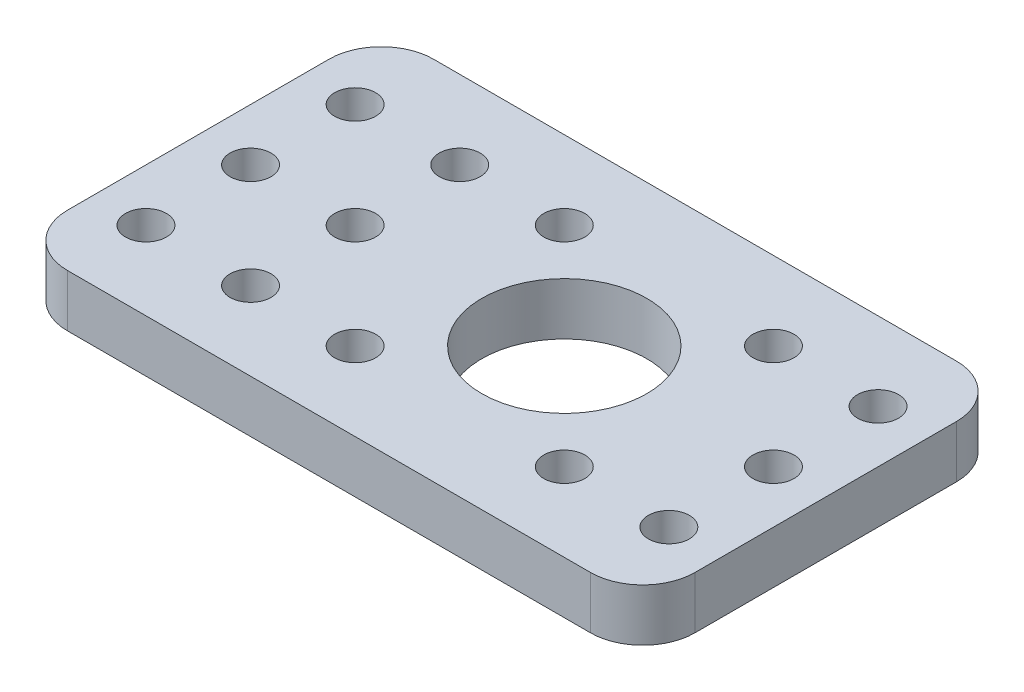
SolidWorks part; units mm, degrees
material "6061-T6 (SS)"
ref_plane "Front Plane" through (0, 0, 0) normal (0, 0, 1) x (1, 0, 0)
ref_plane "Top Plane" through (0, 0, 0) normal (0, 1, 0) x (1, 0, 0)
ref_plane "Right Plane" through (0, 0, 0) normal (1, 0, 0) x (0, 0, -1)
sketch "Sketch1" plane through (0, 0, 0) normal (0, 1, 0) x (1, 0, 0)
  line L1 (0, 0) -> (76.2, 0)
  line L2 (0, 0) -> (0, 44.45)
  line L3 (0, 44.45) -> (76.2, 44.45)
  line L4 (76.2, 0) -> (76.2, 44.45)
  dimension "D1" = 76.2
  dimension "D2" = 44.45
extrude "Boss-Extrude1" add sketch "Sketch1" along normal blind 6.35
fillet "Fillet1" radius 6.35 4 edges at (0, 3.175, -44.45) (76.2, 3.175, -44.45) (0, 3.175, 0) (76.2, 3.175, 0)
sketch "Sketch2" plane through (0, 6.35, 0) normal (0, 1, 0) x (1, 0, 0)
  line L1 (6.35, 0) -> (69.85, 0) construction
  line L3 (76.2, 6.35) -> (76.2, 38.1) construction
  circle A0 centre (31.75, 34.925) radius 2.4892 construction
  circle A1 centre (6.35, 34.925) radius 2.4892 construction
  circle A2 centre (19.05, 34.925) radius 2.4892 construction
  circle A3 centre (19.05, 22.225) radius 2.4892 construction
  circle A4 centre (6.35, 22.225) radius 2.4892 construction
  circle A5 centre (6.35, 9.525) radius 2.4892 construction
  circle A6 centre (19.05, 9.525) radius 2.4892 construction
  circle A7 centre (31.75, 9.525) radius 2.4892 construction
  circle A8 centre (57.15, 9.525) radius 2.4892 construction
  circle A9 centre (69.85, 9.525) radius 2.4892 construction
  circle A10 centre (69.85, 22.225) radius 2.4892 construction
  circle A11 centre (69.85, 34.925) radius 2.4892 construction
  circle A12 centre (57.15, 34.925) radius 2.4892 construction
  circle A14 centre (31.75, 34.925) radius 2.4892
  circle A15 centre (6.35, 34.925) radius 2.4892
  circle A16 centre (19.05, 34.925) radius 2.4892
  circle A17 centre (19.05, 22.225) radius 2.4892
  circle A18 centre (6.35, 22.225) radius 2.4892
  circle A19 centre (6.35, 9.525) radius 2.4892
  circle A20 centre (19.05, 9.525) radius 2.4892
  circle A21 centre (31.75, 9.525) radius 2.4892
  circle A22 centre (57.15, 9.525) radius 2.4892
  circle A23 centre (69.85, 9.525) radius 2.4892
  circle A24 centre (69.85, 22.225) radius 2.4892
  circle A25 centre (69.85, 34.925) radius 2.4892
  circle A26 centre (57.15, 34.925) radius 2.4892
  circle A27 centre (44.45, 22.225) radius 10.0254
  point P45 (76.2, 17.9283)
  dimension "D3" = 20.0508
  dimension "D1" = 22.225
  dimension "D2" = 31.75
extrude "Cut-Extrude1" cut sketch "Sketch2" against normal through all
equation "\"D3@Sketch2\"=20mm+0.002in"
